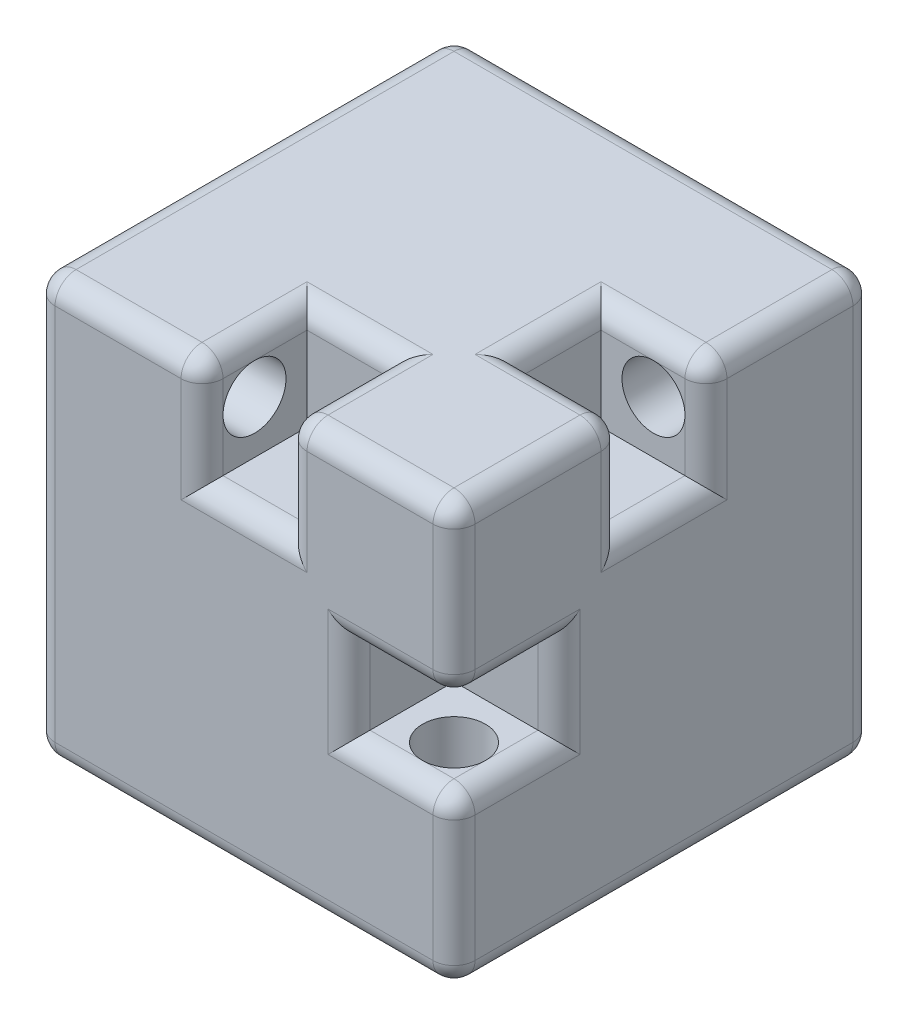
SolidWorks part; units mm, degrees
ref_plane "Front" through (0, 0, 0) normal (0, 0, 1) x (1, 0, 0)
ref_plane "Top" through (0, 0, 0) normal (0, 1, 0) x (1, 0, 0)
ref_plane "Right" through (0, 0, 0) normal (1, 0, 0) x (0, 0, -1)
sketch "Sketch1" plane through (0, 0, 0) normal (0, 1, 0) x (1, 0, 0)
  line L1 (-10, -10) -> (10, -10)
  line L2 (-10, -10) -> (-10, 10)
  line L3 (-10, 10) -> (10, 10)
  line L4 (10, -10) -> (10, 10)
  line L5 (-10, -10) -> (10, 10) construction
  line L6 (-10, 10) -> (10, -10) construction
  point P0 (0, 0)
  dimension "D1" = 20
  dimension "D2" = 20
extrude "Boss-Extrude1" add sketch "Sketch1" along normal blind 20
sketch "Sketch2" plane through (0, 0, 10) normal (0, 0, 1) x (1, 0, 0)
  line L7 (-10, 20) -> (10, 20) construction
  line L8 (-2, 15) -> (2, 15)
  line L9 (-2, 15) -> (-2, 25)
  line L10 (-2, 25) -> (2, 25)
  line L11 (2, 15) -> (2, 25)
  line L12 (-2, 15) -> (2, 25) construction
  line L13 (-2, 25) -> (2, 15) construction
  line L14 (5, 12) -> (5, 8)
  line L15 (5, 12) -> (15, 12)
  line L16 (15, 12) -> (15, 8)
  line L17 (5, 8) -> (15, 8)
  line L18 (5, 12) -> (15, 8) construction
  line L19 (15, 12) -> (5, 8) construction
  point P4 (0, 20)
  point P5 (10, 10)
  point P17 (0, 10)
  dimension "D1" = 10
  dimension "D2" = 4
  dimension "D3" = 2
extrude "Cut-Extrude1" cut sketch "Sketch2" against normal blind 5
sketch "Sketch3" plane through (0, 20, 0) normal (0, 1, 0) x (1, 0, 0)
  line L6 (10, -10) -> (10, 10) construction
  line L7 (5, -2) -> (15, -2)
  line L8 (5, -2) -> (5, 2)
  line L9 (5, 2) -> (15, 2)
  line L10 (15, -2) -> (15, 2)
  line L11 (5, -2) -> (15, 2) construction
  line L12 (5, 2) -> (15, -2) construction
  point P5 (10, 0)
  dimension "D3" = 4
  dimension "D4" = 10
extrude "Cut-Extrude2" cut sketch "Sketch3" against normal blind 5
sketch "Sketch4" plane through (-10, 0, 0) normal (-1, 0, 0) x (0, 0, 1)
  line L0 (10, 20) -> (10, 0) construction
  line L1 (-10, 20) -> (10, 20) construction
  circle A0 centre (7.5, 17.5) radius 1.5
  dimension "D3" = 3
  dimension "D1" = 2.5
  dimension "D2" = 2.5
extrude "Cut-Extrude3" cut sketch "Sketch4" against normal blind 14
sketch "Sketch5" plane through (0, 0, -10) normal (0, 0, -1) x (-1, 0, 0)
  line L0 (-10, 20) -> (10, 20) construction
  line L1 (-10, 20) -> (-10, 0) construction
  circle A0 centre (-7.5, 17.5) radius 1.5
  dimension "D3" = 3
  dimension "D1" = 2.5
  dimension "D2" = 2.5
extrude "Cut-Extrude4" cut sketch "Sketch5" against normal blind 14
sketch "Sketch6" plane through (0, 0, 0) normal (0, -1, 0) x (1, 0, 0)
  line L0 (-10, 10) -> (10, 10) construction
  line L1 (10, 10) -> (10, -10) construction
  circle A0 centre (7.5, 7.5) radius 1.5
  dimension "D3" = 3
  dimension "D1" = 2.5
  dimension "D2" = 2.5
extrude "Cut-Extrude5" cut sketch "Sketch6" against normal blind 14
fillet "Fillet4" radius 1 36 edges at (7.5, 0, 6) (0, 0, -10) (6, 17.5, -10) (10, 17.5, -2) (10, 10, -10) (10, 0, 0) (10, 8, 7.5) (10, 10, 5) (10, 12, 7.5) (10, 17.5, 2) (10, 15, 0) (10, 16, 10) (7.5, 12, 10) (5, 10, 10) (7.5, 8, 10) (10, 4, 10) (0, 0, 10) (-2, 17.5, 10) (0, 15, 10) (2, 17.5, 10) (-10, 10, -10) (-10, 10, 10) (-10, 0, 0) (-10, 17.5, 9) (6, 20, 10) (2, 20, 7.5) (0, 20, 5) (-2, 20, 7.5) (-6, 20, 10) (-10, 20, 0) (0, 20, -10) (10, 20, -6) (7.5, 20, -2) (5, 20, 0) (7.5, 20, 2) (10, 20, 6)
